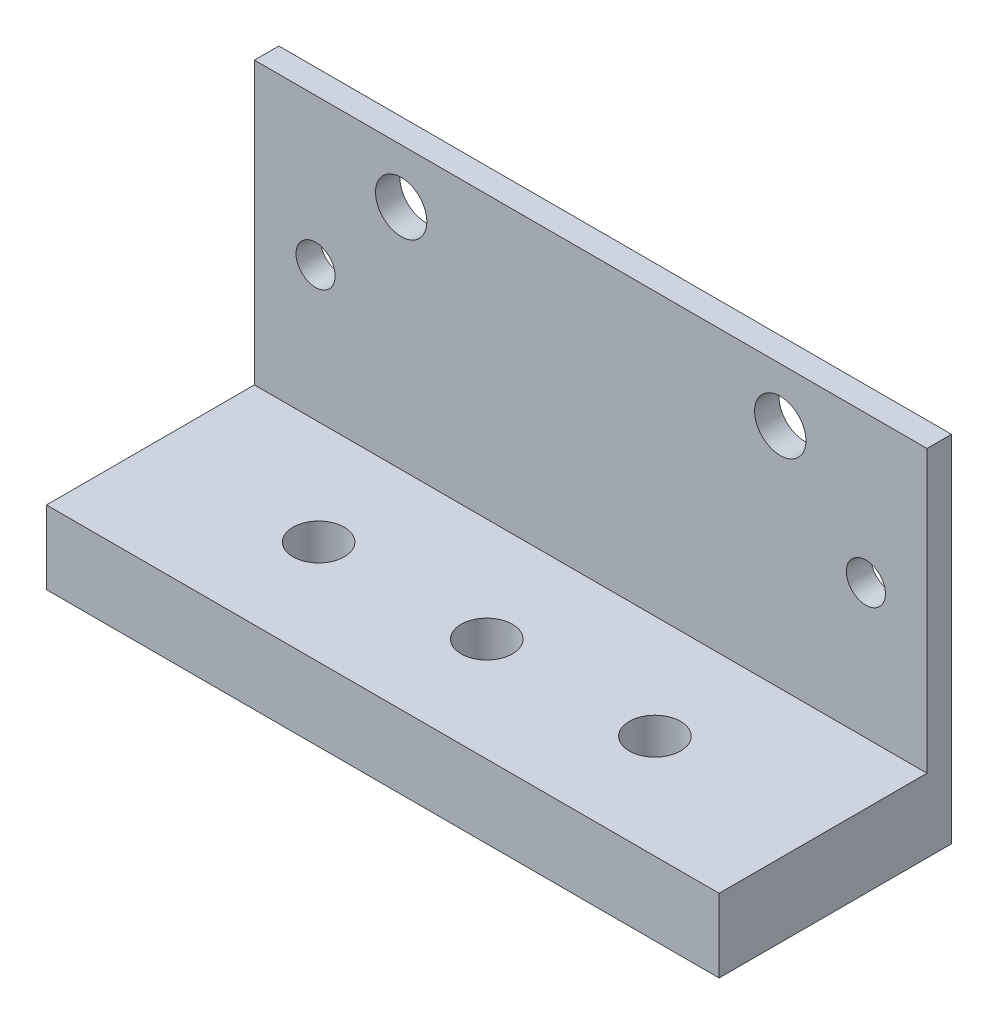
SolidWorks part; units mm, degrees
ref_plane "Front" through (0, 0, 0) normal (0, 0, 1) x (1, 0, 0)
ref_plane "Top" through (0, 0, 0) normal (0, 1, 0) x (1, 0, 0)
ref_plane "Right" through (0, 0, 0) normal (1, 0, 0) x (0, 0, -1)
sketch "Esquisse1" plane through (0, 0, 0) normal (0, 0, 1) x (1, 0, 0)
  line L0 (137.5, 145) -> (137.5, 0) construction
  line L1 (0, 0) -> (275, 0)
  line L2 (0, 0) -> (0, 145)
  line L3 (0, 145) -> (275, 145)
  line L4 (275, 0) -> (275, 145)
  circle A0 centre (60, 123) radius 10.5
  circle A1 centre (25, 85) radius 8
  circle A2 centre (250, 85) radius 8
  circle A3 centre (215, 123) radius 10.5
  dimension "D3" = 21
  dimension "D4" = 16
  dimension "D1" = 145
  dimension "D2" = 275
  dimension "D5" = 25
  dimension "D6" = 60
  dimension "D7" = 60
  dimension "D8" = 22
  dimension "D9" = 137.5
extrude "Boss.-Extru.1" add sketch "Esquisse1" along normal blind 10
sketch "Esquisse2" plane through (0, 0, 0) normal (0, 1, 0) x (1, 0, 0)
  line L1 (275, 0) -> (0, 0)
  line L2 (275, 0) -> (275, -95)
  line L3 (275, -95) -> (0, -95)
  line L4 (0, 0) -> (0, -95)
  dimension "D1" = 95
extrude "Boss.-Extru.2" add sketch "Esquisse2" along normal blind 30
ref_plane "Plan2" through (0, 30, 0) normal (0, 1, 0) x (1, 0, 0)
sketch "Esquisse4" plane through (0, 30, 0) normal (0, 1, 0) x (1, 0, 0)
  line L0 (275, -95) -> (275, -10) construction
  line L1 (0, -95) -> (275, -95) construction
  circle A0 centre (206.25, -52.5) radius 10.5
  circle A1 centre (137.5, -52.5) radius 10.5
  circle A2 centre (68.75, -52.5) radius 10.5
  dimension "D1" = 21
  dimension "D2" = 68.75
  dimension "D4" = 42.5
  dimension "D3" = 3
extrude "Enlèv. mat.-Extru.1" cut sketch "Esquisse4" against normal through all
